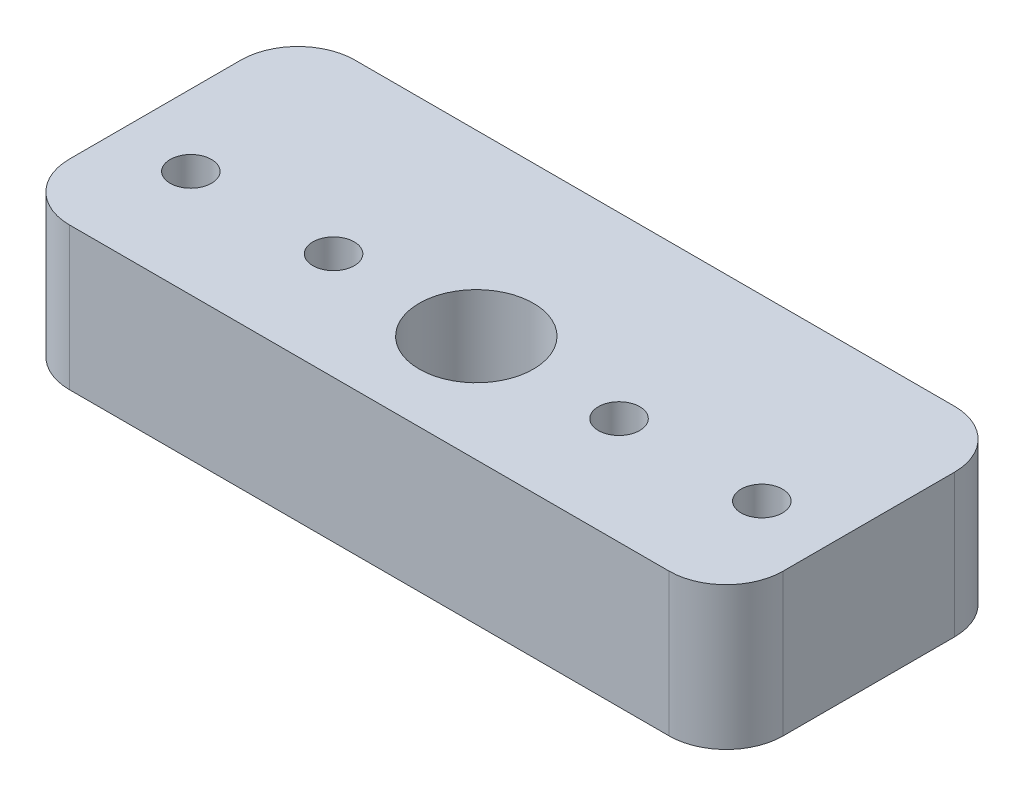
SolidWorks part; units mm, degrees
ref_plane "Front Plane" through (0, 0, 0) normal (0, 0, 1) x (1, 0, 0)
ref_plane "Top Plane" through (0, 0, 0) normal (0, 1, 0) x (1, 0, 0)
ref_plane "Right Plane" through (0, 0, 0) normal (1, 0, 0) x (0, 0, -1)
sketch "Sketch1" plane through (0, 0, 0) normal (0, 1, 0) x (1, 0, 0)
  line L0 (-25, -2.5) -> (25, -2.5) construction
  line L1 (-21, 10) -> (21, 10)
  line L2 (-25, 6) -> (-25, -6)
  line L3 (-21, -10) -> (21, -10)
  line L4 (25, 6) -> (25, -6)
  line L5 (-25, 10) -> (25, -10) construction
  line L6 (-25, -10) -> (25, 10) construction
  line L7 (0, -10) -> (0, 10) construction
  line L8 (25, 10) -> (-25, -10) construction
  arc A0 (-25, -6) -> (-21, -10) centre (-21, -6) ccw
  arc A1 (21, -10) -> (25, -6) centre (21, -6) ccw
  arc A2 (21, 10) -> (25, 6) centre (21, 6) cw
  arc A3 (-21, 10) -> (-25, 6) centre (-21, 6) ccw
  circle A4 centre (0, -2.5) radius 4
  circle A5 centre (10, -2.5) radius 1.45
  circle A6 centre (20, -2.5) radius 1.45
  circle A7 centre (-20, -2.5) radius 1.45
  circle A8 centre (-10, -2.5) radius 1.45
  point P0 (0, 0)
  dimension "D3" = 4
  dimension "D4" = 8
  dimension "D5" = 2.9
  dimension "D6" = 2.9
  dimension "D1" = 20
  dimension "D7" = 7.5
  dimension "D8" = 10
  dimension "D9" = 40
  dimension "D2" = 5
extrude "Boss-Extrude1" add sketch "Sketch1" along normal blind 10
equation "\"Y-ROD-SPACING\"=75"
equation "\"Y-BED-OFFSET\"=2"
equation "\"Y-BED-ROD-INSET\"=3.5"
equation "\"T-SLOT-NUT-FILLET-RADIUS\"=0.5"
equation "\"T-SLOT-SCREW-SHAFT-RADIUS\"=1.55"
equation "\"T-SLOT-SCREW-SHAFT-CUTOUT-LENGTH\"=11.0"
equation "\"T-SLOT-NUT-DEPTH\"=3.5"
equation "\"T-SLOT-NUT-WIDTH\"=2.85"
equation "\"T-SLOT-NUT-END-DISTANCE\"=8"
equation "\"ACRYLIC-TAB-CUTOUT-SIZE\"=\"ACRYLIC-THICKNESS\"+\"ACRYLIC-TAB-TOLERANCE\"*2"
equation "\"ACRYLIC-M3-HOLE\"=2.9"
equation "\"SMOOTHROD-CAP-SCREW-DISTANCE\"=20"
equation "\"D5@Sketch1\"=\"ACRYLIC-M3-HOLE\""
equation "\"D6@Sketch1\"=\"ACRYLIC-M3-HOLE\""
equation "\"D8@Sketch1\"=\"SMOOTHROD-CAP-SCREW-DISTANCE\"/2"
equation "\"ACRYLIC-TAB-WIDTH\"=\"ACRYLIC-THICKNESS\""
equation "\"FRAME-WIDTH-INNER\"=370"
equation "\"NEMA17-HOLE-SPACING\"=31"
equation "\"NEMA17-CENTRAL-CUTOUT\"=22.5"
equation "\"Z-BRACKET-REACH\"=55"
equation "\"TOP-BRACKET-SPACING\"=40"
equation "\"D9@Sketch1\"=\"TOP-BRACKET-SPACING\""
equation "\"D2@Sketch1\"=\"ACRYLIC-TAB-WIDTH\"/2"
equation "\"X-ROD-SPACING\"=45"
equation "\"Z-ROD-SPACING\"=17.5"
equation "\"ACRYLIC-THICKNESS\"=10"
equation "\"ACRYLIC-THICKNESS2\"=4.5"
equation "\"SMOOTHROD-X-LENGTH\"=350"
equation "\"SMOOTHROD-Y-LENGTH\"=350"
equation "\"SMOOTHROD-Z-LENGTH\"=350"
equation "\"SMOOTHROD-TIGHTENING-HEADROOM\"=.25"
equation "\"LEADSCREW-Z-LENGTH\"=300"
equation "\"SCREW-LENGTH-FRAME\"=\"ACRYLIC-THICKNESS\" + 10"
equation "\"SCREW-HEAD-RADIUS\"=6"
equation "\"PRINTED-X-SMOOTHROD-DIAMETER\"=8.4"
equation "\"PRINTED-X-SMOOTHROD-CUTOUT\"=10"
equation "\"PRINTED-X-BASE-HEIGHT\"=10"
equation "\"PRINTED-LM8UU-CUTOUT-SIZE\"=15.5"
equation "\"PRINTED-LM8UU-CUTOUT-LENGTH\"=24.5"
equation "\"PRINTED-X-IDLER-HEIGHT\"=16"
equation "\"PSU-MOUNTING-WIDTH\"=95"
equation "\"PSU-MOUNTING-HEIGHT\"=177"
equation "\"D1@Boss-Extrude1\"=\"ACRYLIC-THICKNESS\""
